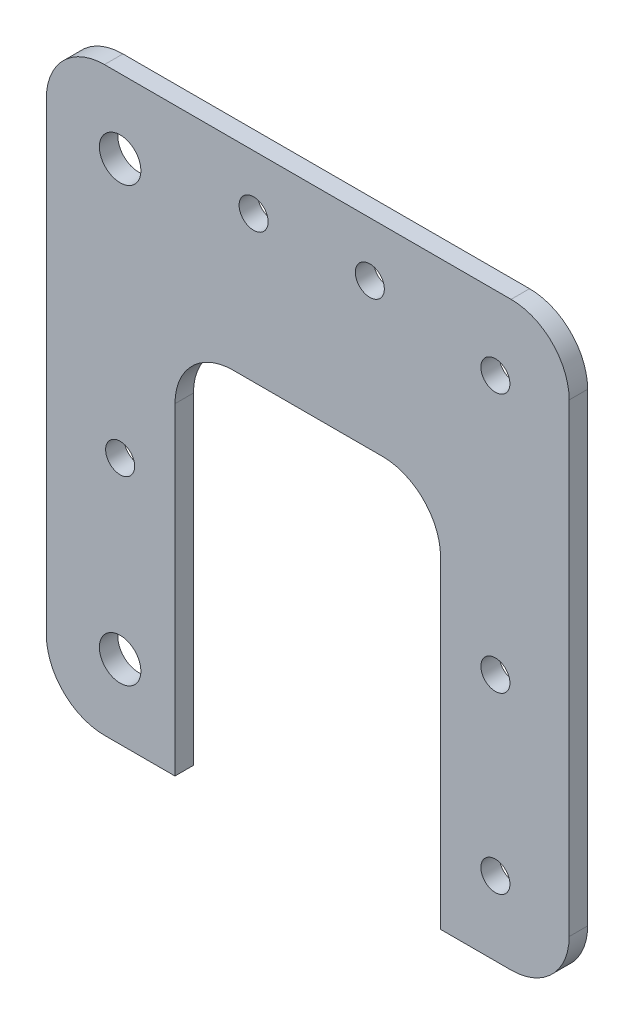
SolidWorks part; units mm, degrees
ref_plane "Front Plane" through (0, 0, 0) normal (0, 0, 1) x (1, 0, 0)
ref_plane "Top Plane" through (0, 0, 0) normal (0, 1, 0) x (1, 0, 0)
ref_plane "Right Plane" through (0, 0, 0) normal (1, 0, 0) x (0, 0, -1)
sketch "Sketch1" plane through (0, 0, 0) normal (0, 0, 1) x (1, 0, 0)
  line L1 (-45, -55) -> (45, -55)
  line L2 (-45, -55) -> (-45, 45)
  line L3 (-45, 45) -> (45, 45)
  line L4 (45, -55) -> (45, 45)
  line L8 (-32.3, 32.3) -> (-32.3, -42.3) construction
  line L9 (-32.3, -42.3) -> (32.3, -42.3) construction
  line L10 (32.3, -42.3) -> (32.3, 32.3) construction
  line L11 (32.3, 32.3) -> (-32.3, 32.3) construction
  line L12 (32.3, -12.3) -> (-32.3, -12.3) construction
  circle A4 centre (32.3, -12.3) radius 2.5
  circle A5 centre (32.3, -42.3) radius 2.5
  circle A6 centre (-32.3, -42.3) radius 3.57
  circle A7 centre (-32.3, -12.3) radius 2.5
  circle A9 centre (-32.3, 32.3) radius 3.57
  circle A11 centre (32.3, 32.3) radius 2.5
  dimension "D9" = 7.14
  dimension "D10" = 5
  dimension "D1" = 90
  dimension "D2" = 100
  dimension "D3" = 12.7
  dimension "D4" = 12.7
  dimension "D5" = 42.7
  dimension "D6" = 12.7
  dimension "D7" = 45
  dimension "D8" = 45
  dimension "D11" = 12.7
extrude "Boss-Extrude1" add sketch "Sketch1" against normal blind 3.18 from offset 19.16
sketch "Sketch2" plane through (0, 0, 15.98) normal (0, 0, -1) x (-1, 0, 0)
  line L0 (45, -55) -> (-45, -55) construction
  line L1 (-22.86, -55) -> (22.86, -55)
  line L2 (-22.86, -55) -> (-22.86, 10.5119)
  line L3 (-22.86, 10.5119) -> (22.86, 10.5119)
  line L4 (22.86, -55) -> (22.86, 10.5119)
  line L5 (0, 0) -> (0, 10.5119) construction
  dimension "D1" = 45.72
extrude "Cut-Extrude1" cut sketch "Sketch2" against normal through all
fillet "Fillet1" radius 10 6 edges at (45, -55, 17.57) (-45, -55, 17.57) (-45, 45, 17.57) (45, 45, 17.57) (-22.86, 10.5119, 17.57) (22.86, 10.5119, 17.57)
ref_plane "Midplane" through (0, -5, 0) normal (0, 1, 0) x (1, 0, 0)
sketch "Sketch3" plane through (0, 0, 19.16) normal (0, 0, 1) x (1, 0, 0)
  circle A0 centre (10.6816, 35.634) radius 2.5 construction
  circle A1 centre (-9.3184, 35.634) radius 2.5 construction
  circle A2 centre (10.6816, 35.634) radius 2.5
  circle A3 centre (-9.3184, 35.634) radius 2.5
extrude "Cut-Extrude2" cut sketch "Sketch3" against normal through all
